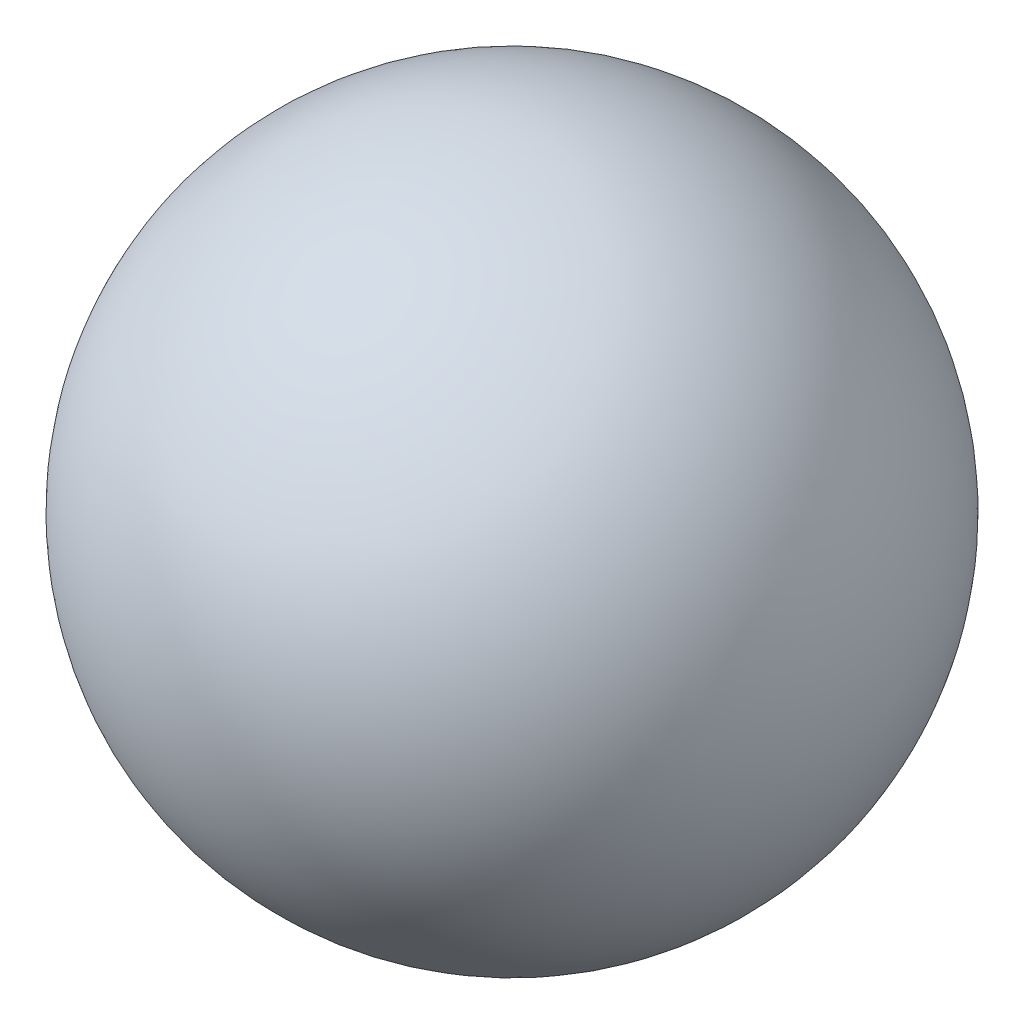
SolidWorks part; units mm, degrees
ref_plane "Front Plane" through (0, 0, 0) normal (0, 0, 1) x (1, 0, 0)
ref_plane "Top Plane" through (0, 0, 0) normal (0, 1, 0) x (1, 0, 0)
ref_plane "Right Plane" through (0, 0, 0) normal (1, 0, 0) x (0, 0, -1)
sketch "Sketch1" plane through (0, 0, 0) normal (0, 1, 0) x (1, 0, 0)
  line L0 (-1.75, 0) -> (1.75, 0) construction
  line L1 (-1.75, 0) -> (1.75, 0)
  circle A0 centre (0, 0) radius 1.75
  dimension "D1" = 3.5
revolve "Revolve1" add sketch "Sketch1" angle 360 about L1 region at (0, 0, -0.7427)
equation "\"bearing_21_OD\"= 21mm"
equation "\"pin_cirlce_diameter\"= 75mm"
equation "\"pin_diam\"= 6mm"
equation "\"gear_thickness\"= 4mm"
equation "\"ball_bearing_diam\"= 3.214mm"
equation "\"bearing_21_outer_clearance\"= 0.127mm'change this"
equation "\"bearing_15_OD\"= 15mm"
equation "\"bearing_15_outer_clearance\"= 0mm'change this"
equation "\"thrust_bearing_thickness\"= 5mm'measure this irl and change"
equation "\"D1@Sketch1\"=3.5mm"
